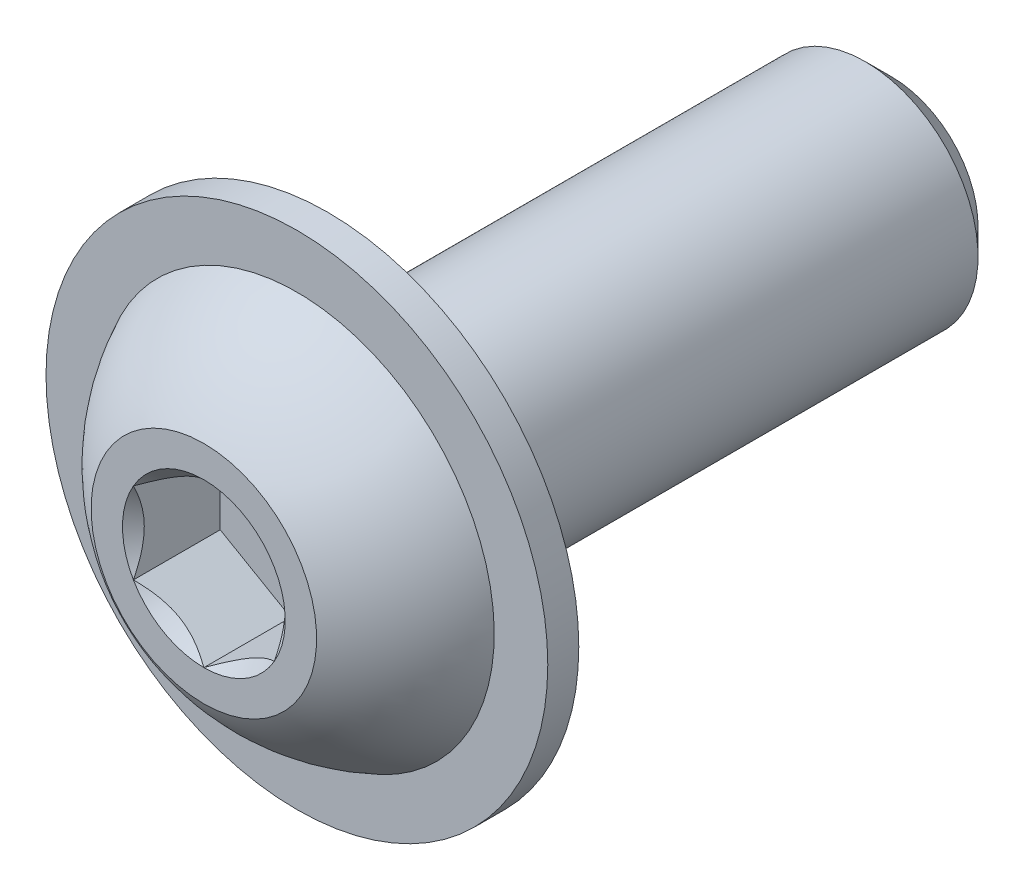
SolidWorks part; units mm, degrees
material "AISI 304"
ref_plane "Front" through (0, 0, 0) normal (0, 0, 1) x (1, 0, 0)
ref_plane "Top" through (0, 0, 0) normal (0, 1, 0) x (1, 0, 0)
ref_plane "Right" through (0, 0, 0) normal (1, 0, 0) x (0, 0, -1)
sketch "Sketch1" plane through (0, 0, 0) normal (1, 0, 0) x (0, 0, -1)
  line L2 (4.4, 4) -> (24.4, 4)
  line L3 (24.4, 4) -> (24.4, 0)
  line L4 (24.4, 0) -> (4.4, 0)
  line L6 (3.3, 7) -> (4.4, 7) construction
  line L7 (24.4, 4) -> (24.4, -4) construction
  line L8 (0, 0) -> (4.4, 0) construction
  line L9 (4.4, 7) -> (4.4, -7) construction
  line L11 (4.4, 4) -> (4.4, 0)
  line L13 (0, 2.5) -> (0, -2.5) construction
  line L14 (0, 2.5) -> (0, 4) construction
  line L15 (3.3, 7) -> (3.3, 8.9) construction
  line L16 (3.3, 8.9) -> (4.4, 8.9) construction
  line L17 (4.4, 8.9) -> (4.4, 7) construction
  line L18 (4.4, 8.9) -> (4.4, -8.9) construction
  arc A3 (0, 4) -> (3.3, 7) centre (6.65, 0) cw construction
  dimension "D1" = 1.1
revolve "Revolve1" add sketch "Sketch1" angle 360 mid plane about L4
sketch "Sketch3" plane through (0, 0, -24.4) normal (0, 0, -1) x (-1, 0, 0)
  circle A0 centre (0, 0) radius 4
curve "Helix/Spiral1" pitch 1.25 height 21.25 turns 17
sketch "Sketch2" plane through (0, 0, 0) normal (1, 0, 0) x (0, 0, -1)
  line L0 (24.4, 4) -> (25.4937, 4)
  line L1 (25.4937, 4) -> (25.025, 3.1881)
  line L2 (25.025, 3.1881) -> (24.8687, 3.1881)
  line L3 (24.8687, 3.1881) -> (24.4, 4)
  line L4 (24.6344, 3.5941) -> (25.2594, 3.5941) construction
  dimension "D1" = 60
  dimension "D2" = 0.1562
  dimension "D3" = 0.625
chamfer "Chamfer1" distance 0.9375 angle 45 1 edges at (0, 4, -24.4)
sweep "Cut-Sweep1" [suppressed] cut profiles "Sketch2" path "Helix/Spiral1"
sketch "Sketch7" plane through (0, 0, 0) normal (1, 0, 0) x (0, 0, -1)
  line L6 (3.3, 7) -> (4.4, 7) construction
  line L8 (0, 0) -> (4.4, 0) construction
  line L11 (4.4, 7) -> (4.4, -7) construction
  line L12 (3.3, 7) -> (4.4, 7)
  line L13 (0, 0) -> (4.4, 0)
  line L14 (0, 2.5) -> (0, -2.5) construction
  line L15 (4.4, 7) -> (4.4, 0)
  line L16 (0, 4) -> (0, 0)
  arc A2 (3.3, 7) -> (0, 4) centre (6.65, 0) ccw construction
  arc A3 (3.3, 7) -> (0, 4) centre (6.65, 0) ccw
revolve "Revolve2" add sketch "Sketch7" angle 360 mid plane about L13
sketch "Sketch11" plane through (0, 0, -4.4) normal (0, 0, -1) x (-1, 0, 0)
  circle A0 centre (0, 0) radius 8.9
extrude "Boss-Extrude3" add sketch "Sketch11" against normal up to vertex (1.1 mm away) up to point (0, 7, -3.3)
sketch "Sketch5" plane through (0, 0, 0) normal (0, 0, 1) x (1, 0, 0)
  line L1 (2.5, -1.4434) -> (2.5, 1.4434)
  line L2 (2.5, 1.4434) -> (0, 2.8868)
  line L3 (0, 2.8868) -> (-2.5, 1.4434)
  line L4 (-2.5, 1.4434) -> (-2.5, -1.4434)
  line L5 (-2.5, -1.4434) -> (0, -2.8868)
  line L6 (0, -2.8868) -> (2.5, -1.4434)
  circle A0 centre (0, 0) radius 2.5 construction
extrude "Cut-Extrude2" cut sketch "Sketch5" against normal blind 3.08
sketch "Sketch6" plane through (0, 0, 0) normal (0, 0, 1) x (1, 0, 0)
  circle A0 centre (0, 0) radius 2.8868
extrude "Cut-Extrude3" cut sketch "Sketch6" against normal blind 3.08 draft 45
sketch "Sketch9" [suppressed] plane through (0, 0, -5.0546) normal (0, 0, 1) x (1, 0, 0)
  circle A2 centre (0, 0) radius 4.7625
extrude "Boss-Extrude2" [suppressed] add sketch "Sketch9" against normal offset from surface (6.35 mm away) 31.75
sketch "Sketch10" plane through (0, 0, 0) normal (1, 0, 0) x (0, 0, -1)
  line L0 (24.4, 4) -> (24.4, -4) construction
  point P0 (22.525, -4)
  dimension "D1" = 1.875
equation "\"D3@Helix/Spiral1\" = \"Lg@Sketch1\" + \"D4@Helix/Spiral1\""
equation "\"D2@Sketch2\" = \"D4@Helix/Spiral1\" * .125"
equation "\"D3@Sketch2\" = \"D4@Helix/Spiral1\" * .5"
equation "\"D1@Chamfer1\" = \"D4@Helix/Spiral1\" * .75"
equation "\"D1@Cut-Extrude2\" = \"Head Ht@Sketch1\" * .7"
equation "\"D1@Sketch1\" = \"Head Ht@Sketch1\" * .25"
equation "\"D1@Sketch10\" = \"D4@Helix/Spiral1\" * 1.5"
equation "\"D1@Cut-Extrude3\" = \"D1@Cut-Extrude2\""
